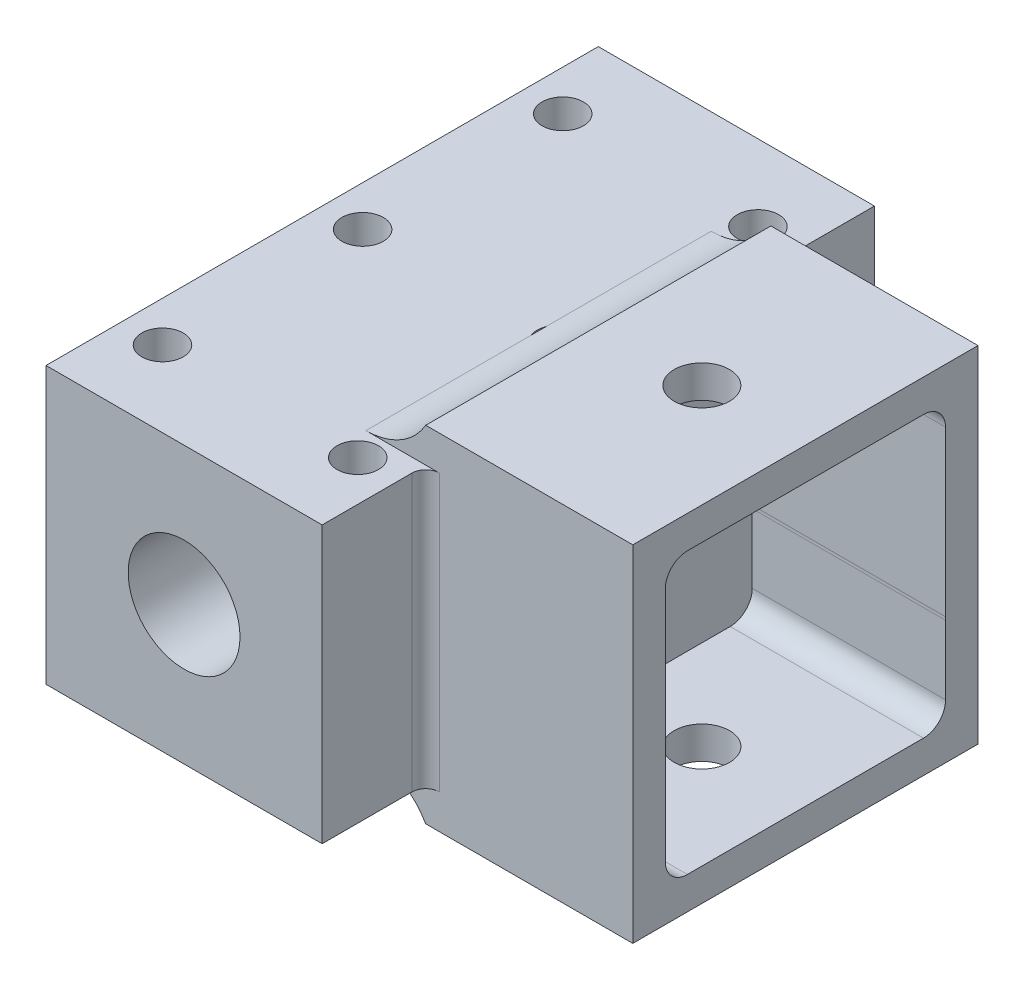
SolidWorks part; units mm, degrees
ref_plane "Front Plane" through (0, 0, 0) normal (0, 0, 1) x (1, 0, 0)
ref_plane "Top Plane" through (0, 0, 0) normal (0, 1, 0) x (1, 0, 0)
ref_plane "Right Plane" through (0, 0, 0) normal (1, 0, 0) x (0, 0, -1)
sketch "Sketch2" plane through (0, 0, 0) normal (0, 0, 1) x (1, 0, 0)
  line L1 (-20, -20) -> (20, -20)
  line L2 (-20, -20) -> (-20, 20)
  line L3 (-20, 20) -> (20, 20)
  line L4 (20, -20) -> (20, 20)
  line L5 (-20, -20) -> (20, 20) construction
  line L6 (-20, 20) -> (20, -20) construction
  circle A0 centre (0, 0) radius 8.1
  point P0 (0, 0)
  dimension "D1" = 16.2
  dimension "D2" = 40
extrude "Boss-Extrude1" add sketch "Sketch2" along normal blind 80
sketch "Sketch3" plane through (0, 20, 0) normal (0, 1, 0) x (1, 0, 0)
sketch "Sketch4" plane through (20, 0, 0) normal (1, 0, 0) x (0, 0, -1)
  line L0 (-80, 20) -> (-25.68, -7.16) construction
  line L1 (0, 20) -> (-25.8797, 7.0602) construction
  line L2 (-46.9, 20.1) -> (-60.1, 20.1) construction
  line L3 (-19.9, 17.1) -> (-19.9, 7.1) construction
  line L4 (-57.1, 20.1) -> (-46.9, 20.1) construction
  line L5 (-19.9, -20.1) -> (-19.9, -7.1) construction
  line L6 (-19.9, 20.1) -> (-22.9, 20.1) construction
  line L7 (-19.9, -20.1) -> (-60.1, 20.1) construction
  line L8 (-19.9, 20.1) -> (-40, 0) construction
  line L9 (-44.7, 17.9) -> (-44.7, 16.72) construction
  line L10 (-45.7399, 7.2955) -> (-49.12, 10.6756) construction
  line L12 (-47.1, 14.32) -> (-47.4605, 14.32) construction
  line L14 (-21.9, 4.7) -> (-23.28, 4.7) construction
  line L16 (-35.3, 17.9) -> (-35.3, 16.72) construction
  line L17 (-34.2601, 7.2955) -> (-30.88, 10.6756) construction
  line L18 (-32.7045, 5.7399) -> (-29.3244, 9.12) construction
  line L19 (-32.9, 14.32) -> (-32.5395, 14.32) construction
  line L20 (-25.68, 7.1) -> (-25.68, 7.4605) construction
  line L21 (-19.9, -17.1) -> (-19.9, -7.1) construction
  line L24 (-25.68, -7.1) -> (-25.68, -7.4605) construction
  line L27 (-65, -25) -> (-15, -25)
  line L28 (-65, -25) -> (-65, 25)
  line L29 (-65, 25) -> (-15, 25)
  line L30 (-15, -25) -> (-15, 25)
  line L31 (-65, -25) -> (-60.1, -20.1) construction
  line L32 (-65, 25) -> (-15, -25) construction
  line L33 (-22.9, -20.1) -> (-32.9, -20.1) construction
  line L34 (-40, 0) -> (-15, 25) construction
  line L35 (-59.2213, -19.2213) -> (-58.6948, -18.6948) construction
  line L36 (-60.1, 17.1) -> (-60.1, 6.9) construction
  line L37 (-57.1, -20.1) -> (-47.1, -20.1) construction
  line L38 (-60.1, -17.1) -> (-60.1, -6.9) construction
  line L39 (-60.1, 6.9) -> (-60.1, -6.9) construction
  line L40 (-47.1, -20.1) -> (-32.9, -20.1) construction
  line L60 (-57.1, 20.3) -> (-46.9, 20.3)
  line L62 (-44.5, 17.9) -> (-44.5, 16.72)
  line L63 (-47.1, 14.12) -> (-47.4605, 14.12)
  line L68 (-22.9, 20.3) -> (-33.1, 20.3)
  line L69 (-19.7, 17.1) -> (-19.7, 7.1093)
  line L71 (-25.88, 7.1) -> (-25.88, 7.4605)
  line L74 (-25.88, -7.1) -> (-25.88, -7.4605)
  line L76 (-19.7, -17.1) -> (-19.7, -7.1093)
  line L77 (-22.9, -20.3) -> (-32.9, -20.3)
  line L78 (-47.1, -20.3) -> (-32.9, -20.3)
  line L79 (-57.1, -20.3) -> (-47.1, -20.3)
  line L80 (-60.3, -17.1) -> (-60.3, -6.9)
  line L81 (-60.3, 6.9) -> (-60.3, -6.9)
  line L82 (-60.3, 17.1) -> (-60.3, 6.9)
  line L84 (-19.7, -6.6743) -> (-19.7, -7.1093)
  line L85 (-32.3974, 3.8013) -> (-80, -20) construction
  line L86 (-45.5984, 7.4369) -> (-48.9736, 10.812) construction
  line L87 (-34.4016, 7.4369) -> (-31.0264, 10.812) construction
  line L88 (-32.9, 14.12) -> (-32.5395, 14.12) construction
  line L89 (-35.5, 17.9) -> (-35.5, 16.72) construction
  line L90 (-21.8915, 4.5) -> (-23.28, 4.5) construction
  line L91 (-32.5631, 5.5984) -> (-29.188, 8.9736) construction
  line L92 (-21.8915, -4.5) -> (-23.28, -4.5) construction
  line L93 (-21.9, -4.7) -> (-23.28, -4.7) construction
  line L94 (-19.9, -10.05) -> (0, -20) construction
  line L95 (-32.5631, -5.5984) -> (-29.188, -8.9736) construction
  line L96 (-32.7045, -5.7399) -> (-29.3244, -9.12) construction
  line L97 (-19.9, -5.9103) -> (-19.9, 5.9103) construction
  line L99 (-22.9, 20.1) -> (-33.1, 20.1) construction
  line L100 (-19.9, 17.1) -> (-19.9, 20.1) construction
  line L101 (-46.9, 20.3) -> (-33.1, 20.3)
  line L102 (-19.7, 7.1093) -> (-19.7, -6.6743)
  arc A1 (-57.1, 20.1) -> (-60.1, 17.1) centre (-57.1, 17.1) ccw construction
  arc A2 (-47.4605, 14.32) -> (-49.12, 10.6756) centre (-47.4605, 12.12) ccw construction
  arc A3 (-44.7, 16.72) -> (-47.1, 14.32) centre (-47.1, 16.72) cw construction
  arc A5 (-19.9, 17.1) -> (-22.9, 20.1) centre (-22.9, 17.1) ccw construction
  arc A7 (-35.3, 16.72) -> (-32.9, 14.32) centre (-32.9, 16.72) ccw construction
  arc A8 (-25.68, 7.4605) -> (-29.3244, 9.12) centre (-27.88, 7.4605) ccw construction
  arc A9 (-32.5395, 14.32) -> (-30.88, 10.6756) centre (-32.5395, 12.12) cw construction
  arc A10 (-23.28, 4.7) -> (-25.68, 7.1) centre (-23.28, 7.1) cw construction
  arc A13 (-22.9, -20.1) -> (-19.9, -17.1) centre (-22.9, -17.1) ccw construction
  arc A18 (-57.1, -20.1) -> (-60.1, -17.1) centre (-57.1, -17.1) cw construction
  arc A19 (-35.7265, 7.1153) -> (-44.2735, 7.1153) centre (-40, 0) ccw construction
  arc A20 (-32.8847, -4.2735) -> (-32.8847, 4.2735) centre (-40, 0) ccw construction
  arc A21 (-34.2601, 7.2955) -> (-35.7265, 7.1153) centre (-35.1087, 8.144) cw construction
  arc A22 (-32.7045, 5.7399) -> (-32.8847, 4.2735) centre (-31.856, 4.8913) ccw construction
  arc A23 (-32.7045, -5.7399) -> (-32.8847, -4.2735) centre (-31.856, -4.8913) cw construction
  arc A24 (-45.7399, 7.2955) -> (-44.2735, 7.1153) centre (-44.8913, 8.144) ccw construction
  arc A53 (-19.7, 17.1) -> (-22.9, 20.3) centre (-22.9, 17.1) ccw
  arc A55 (-25.8797, 7.0602) -> (-25.88, 7.1) centre (-23.28, 7.1) cw
  arc A61 (-25.8797, -7.0602) -> (-25.88, -7.1) centre (-23.28, -7.1) ccw
  arc A62 (-19.7, -7.1093) -> (-19.7, -6.6743) centre (-22.0901, -6.8918) ccw
  arc A63 (-22.9, -20.3) -> (-19.7, -17.1) centre (-22.9, -17.1) ccw
  arc A64 (-57.1, -20.3) -> (-60.3, -17.1) centre (-57.1, -17.1) cw
  arc A65 (-57.1, 20.3) -> (-60.3, 17.1) centre (-57.1, 17.1) ccw
  arc A66 (-46.9, 20.3) -> (-44.5, 17.9) centre (-46.9, 17.9) cw construction
  arc A67 (-44.5, 16.72) -> (-47.1, 14.12) centre (-47.1, 16.72) cw construction
  arc A68 (-47.4605, 14.12) -> (-48.9736, 10.812) centre (-47.4605, 12.12) ccw construction
  arc A69 (-45.5984, 7.4369) -> (-44.3764, 7.2867) centre (-44.8913, 8.144) ccw construction
  arc A70 (-35.6236, 7.2867) -> (-44.3764, 7.2867) centre (-40, 0) ccw construction
  arc A71 (-34.4016, 7.4369) -> (-35.6236, 7.2867) centre (-35.1087, 8.144) cw construction
  arc A72 (-32.5395, 14.12) -> (-31.0264, 10.812) centre (-32.5395, 12.12) cw construction
  arc A73 (-35.5, 16.72) -> (-32.9, 14.12) centre (-32.9, 16.72) ccw construction
  arc A74 (-33.1, 20.3) -> (-35.5, 17.9) centre (-33.1, 17.9) ccw construction
  arc A75 (-19.7, 7.1093) -> (-21.8915, 4.5) centre (-22.0901, 6.8918) cw construction
  arc A76 (-23.28, 4.5) -> (-25.88, 7.1) centre (-23.28, 7.1) cw construction
  arc A77 (-25.88, 7.4605) -> (-29.188, 8.9736) centre (-27.88, 7.4605) ccw construction
  arc A78 (-32.5631, 5.5984) -> (-32.7133, 4.3764) centre (-31.856, 4.8913) ccw construction
  arc A79 (-32.7133, -4.3764) -> (-32.7133, 4.3764) centre (-40, 0) ccw construction
  arc A80 (-19.7, -7.1093) -> (-21.8915, -4.5) centre (-22.0901, -6.8918) ccw construction
  arc A81 (-19.9, -7.1) -> (-21.9, -4.7) centre (-22.0901, -6.8918) ccw construction
  arc A82 (-23.28, -4.7) -> (-25.68, -7.1) centre (-23.28, -7.1) ccw construction
  arc A83 (-23.28, -4.5) -> (-25.88, -7.1) centre (-23.28, -7.1) ccw construction
  arc A84 (-25.68, -7.4605) -> (-29.3244, -9.12) centre (-27.88, -7.4605) cw construction
  arc A85 (-25.88, -7.4605) -> (-29.188, -8.9736) centre (-27.88, -7.4605) cw construction
  arc A86 (-32.5631, -5.5984) -> (-32.7133, -4.3764) centre (-31.856, -4.8913) cw construction
  arc A87 (-19.9, 7.1) -> (-21.9, 4.7) centre (-22.0901, 6.8918) cw construction
  arc A88 (-33.1, 20.1) -> (-35.3, 17.9) centre (-33.1, 17.9) ccw construction
  arc A89 (-46.9, 20.1) -> (-44.7, 17.9) centre (-46.9, 17.9) cw construction
  point P8 (-40, 0)
  point P30 (-62.7304, 12.4703)
  point P33 (-56.9504, 12.4703)
  point P36 (-52.3947, 21.8903)
  point P39 (-52.3947, 18.8903)
  point P96 (-42.6304, 7.5703)
  line M4 (0, 20) -> (-80, 20)
  line M6 (-80, -20) -> (0, -20)
  dimension "D3" = 3
  dimension "D5" = 1.2
  dimension "D6" = 1.2
  dimension "D7" = 8.3
  dimension "D9" = 2.4
  dimension "D1" = 5.78
  dimension "D4" = 50
  dimension "D11" = 1.1
  dimension "D12" = 1.1
  dimension "D13" = 0.2
extrude "Boss-Extrude2" add sketch "Sketch4" along normal blind 30 contours A65 L28 A64 L80 L81 L82 M4 M6 | A65 L60 L101 L68 A53 L30 L29 L28 M4 | A63 L30 A53 L69 L102 A62 L76 M6 M4 | L79 A64 L28 L27 L30 A63 L77 L78 M6 region at (20, -22.6062, 40) region at (20, 0, 62.6048) region at (20, 0.0001, 17.3952) region at (20, 22.6062, 40)
sketch "Sketch7" plane through (20, 0, 0) normal (1, 0, 0) x (0, 0, -1)
  line L0 (-65, -25) -> (-15, -25) construction
  line L1 (-65, 25) -> (-15, 25)
  line L2 (-65, 25) -> (-65, -25)
  line L3 (-65, -25) -> (-15, -25)
  line L4 (-15, 25) -> (-15, -25)
extrude "Boss-Extrude4" add sketch "Sketch7" along normal blind 2
fillet "Fillet6" radius 2 2 edges at (20, 0, 15) (20, 0, 65)
fillet "Fillet7" radius 10 2 edges at (20, 20, 40) (20, -20, 40)
sketch "Sketch8" plane through (0, -25, 0) normal (0, -1, 0) x (1, 0, 0)
  line L0 (20, 15) -> (50, 65) construction
  line L1 (20, 65) -> (50, 15) construction
  circle A0 centre (35, 40) radius 4
  dimension "D1" = 8
extrude "Cut-Extrude4" cut sketch "Sketch8" against normal blind 75
sketch "Sketch9" plane through (0, 0, 15) normal (0, 0, -1) x (-1, 0, 0)
  line L0 (-35, 25) -> (-35, -27.872) construction
  line L1 (-50, 25) -> (-20, 25) construction
  line L2 (-35, 29.3048) -> (-35, 25) construction
sketch "Sketch16" plane through (0, 0, 0) normal (0, 0, -1) x (-1, 0, 0)
  line L0 (0, 23.7077) -> (0, -24.4086) construction
sketch "Sketch17" plane through (0, 20, 0) normal (0, 1, 0) x (1, 0, 0)
  line L0 (14.1407, -80) -> (14.1407, 0) construction
  line L1 (20, -80) -> (-20, -80) construction
  line L2 (20, 0) -> (-20, 0) construction
  line L3 (50, -40) -> (-20, -40) construction
  line L4 (50, -65) -> (50, -15) construction
  line L5 (-20, -80) -> (-20, 0) construction
  line L6 (0, 0) -> (0, -80) construction
  circle A0 centre (14.1407, -11.014) radius 3
  circle A1 centre (14.1407, -40) radius 3
  circle A2 centre (14.1407, -68.986) radius 3
  circle A3 centre (-14.1407, -68.986) radius 3
  circle A4 centre (-14.1407, -40) radius 3
  circle A5 centre (-14.1407, -11.014) radius 3
  dimension "D1" = 6
extrude "Cut-Extrude5" cut sketch "Sketch17" against normal blind 54
